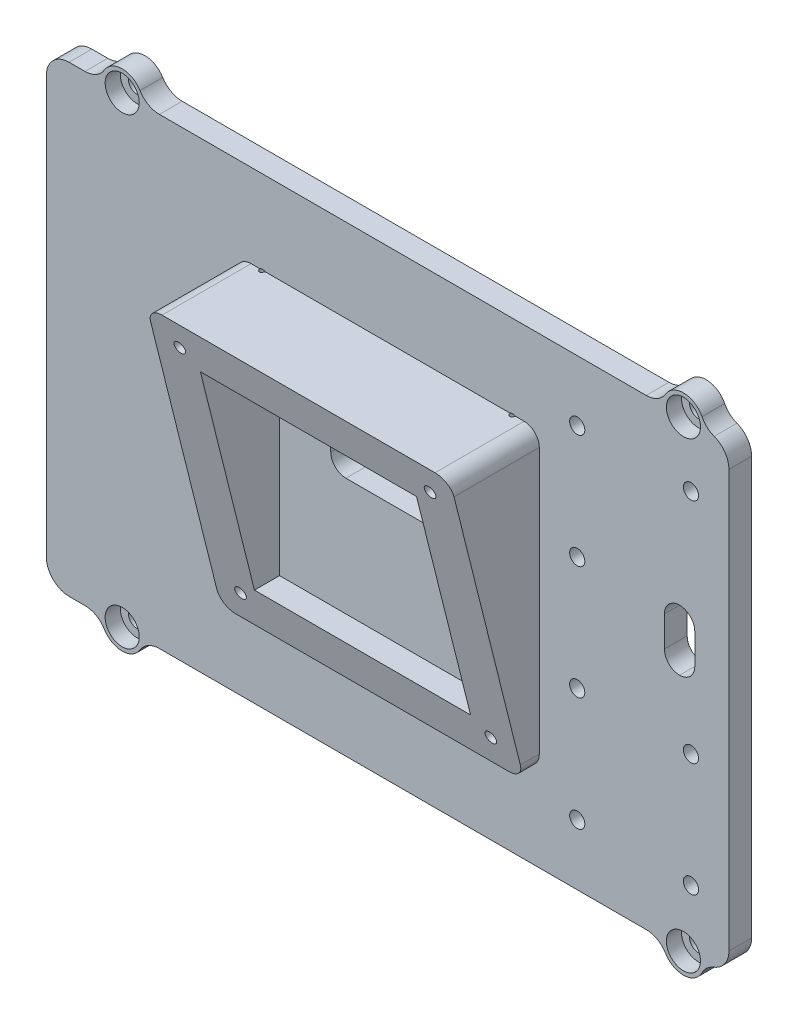
SolidWorks part; units mm, degrees
ref_plane "Спереди" through (0, 0, 0) normal (0, 0, 1) x (1, 0, 0)
ref_plane "Сверху" through (0, 0, 0) normal (0, 1, 0) x (1, 0, 0)
ref_plane "Справа" through (0, 0, 0) normal (1, 0, 0) x (0, 0, -1)
sketch "Эскиз1" plane through (0, 0, 0) normal (0, 1, 0) x (1, 0, 0)
  line L0 (0, 45) -> (0, -45) construction
  line L1 (-30.5, 45) -> (30.5, 45)
  line L2 (-30.5, 45) -> (-30.5, -45)
  line L3 (-30.5, -45) -> (30.5, -45)
  line L4 (30.5, 45) -> (30.5, -45)
  line L6 (-30.5, 0) -> (30.5, 0) construction
  point P8 (0, 0)
  dimension "D1" = 90
  dimension "D2" = 61
extrude "боковые стенки" [suppressed] add sketch "Эскиз1" along normal blind 18
sketch "Эскиз7" plane through (0, 0, 0) normal (0, 1, 0) x (1, 0, 0)
  line L1 (-30.5, 45) -> (30.5, 45)
  line L2 (-30.5, 45) -> (-30.5, -45)
  line L3 (-30.5, -45) -> (30.5, -45)
  line L4 (30.5, 45) -> (30.5, -45)
extrude "крышка" [suppressed] add sketch "Эскиз7" along normal blind 12
dome "Купол6" [suppressed] faces to dome 1 distance 10 parameters "D1"=10
shell "Оболочка1" [suppressed] thickness 2
sketch "Эскиз11" [suppressed] plane through (-30.5, 0, 0) normal (-1, 0, 0) x (0, 0, 1)
  line L1 (-45, 30) -> (45, 30) construction
  line L2 (0, 30) -> (45, 30)
  line L4 (45, 30) -> (45, 18)
  ellipse E0 centre (0, 18) end of major axis (-45, 18) minor radius 12 (45, 18) -> (0, 30) ccw
  dimension "D1" = 12
extrude "скругление вдоль" [suppressed] cut sketch "Эскиз11" against normal through all
sketch "Эскиз12" [suppressed] plane through (0, 0, -45) normal (0, 0, -1) x (-1, 0, 0)
  line L0 (-30.5, 30) -> (-30.5, 0) construction
  line L1 (-30.5, 18) -> (-30.5, 30)
  line L2 (-30.5, 30) -> (30.5, 30) construction
  line L3 (-30.5, 30) -> (0, 30)
  ellipse E0 centre (0, 18) end of major axis (-30.5, 18) minor radius 12 (0, 30) -> (-30.5, 18) ccw
  dimension "D1" = 12
extrude "скругление поперек" [suppressed] cut sketch "Эскиз12" against normal through all
mirror "Зеркальное отражение3" [suppressed] about plane through (0, 0, 0) normal (0, 0, 1)
mirror "Зеркальное отражение4" [suppressed] about plane through (0, 0, 0) normal (1, 0, 0)
shell "Оболочка5" [suppressed] thickness 2.1
sketch "Эскиз13" [suppressed] plane through (30.5, 0, 0) normal (1, 0, 0) x (0, 0, -1)
  line L0 (-45, 30) -> (-45, 0) construction
  line L1 (-36.15, 1) -> (-27.65, 1)
  line L2 (-36.15, 1) -> (-36.15, 0)
  line L3 (-36.15, 0) -> (-27.65, 0)
  line L4 (-27.65, 1) -> (-27.65, 0)
  line L5 (-45, 0) -> (45, 0) construction
  dimension "D1" = 8.5
  dimension "D3" = 8.85
  dimension "D4" = 1
extrude "отверстие для microusb" [suppressed] cut sketch "Эскиз13" against normal up to surface (2.1 mm away)
sketch "Эскиз14" [suppressed] plane through (30.5, 0, 0) normal (1, 0, 0) x (0, 0, -1)
  line L0 (-45, 30) -> (-45, 0) construction
  line L1 (-18.5, 4.5) -> (-2.5, 4.5)
  line L2 (-18.5, 4.5) -> (-18.5, 0)
  line L3 (-18.5, 0) -> (-2.5, 0)
  line L4 (-2.5, 4.5) -> (-2.5, 0)
  line L5 (-45, 0) -> (-36.15, 0) construction
  line L6 (-27.65, 0) -> (45, 0) construction
  dimension "D1" = 16
  dimension "D3" = 26.5
  dimension "D4" = 4.5
extrude "отверстие для hdmi" [suppressed] cut sketch "Эскиз14" against normal up to surface (2.1 mm away)
sketch "Эскиз15" [suppressed] plane through (30.5, 0, 0) normal (1, 0, 0) x (0, 0, -1)
  line L0 (-45, 30) -> (-45, 0) construction
  line L1 (-2.5, 0) -> (45, 0) construction
  circle A0 centre (11, 0.1) radius 3.5
  dimension "D1" = 7
  dimension "D2" = 56
  dimension "D3" = 0.1
extrude "отверстие для audio" [suppressed] cut sketch "Эскиз15" against normal up to surface (2.1 mm away)
sketch "Эскиз16" [suppressed] plane through (0, 0, -45) normal (0, 0, -1) x (-1, 0, 0)
  line L0 (-30.5, 0) -> (30.5, 0) construction
  line L1 (-26.5, 0) -> (-9, 0)
  line L2 (-26.5, 0) -> (-26.5, 11.5)
  line L3 (-26.5, 11.5) -> (-9, 11.5)
  line L4 (-9, 0) -> (-9, 11.5)
  line L5 (-30.5, 30) -> (-30.5, 0) construction
  dimension "D1" = 4
  dimension "D2" = 11.5
  dimension "D3" = 17.5
extrude "отверстие для ethernet" [suppressed] cut sketch "Эскиз16" against normal up to surface (2.1 mm away)
sketch "Эскиз17" [suppressed] plane through (0, 0, -45) normal (0, 0, -1) x (-1, 0, 0)
  line L0 (-9, 0) -> (30.5, 0) construction
  line L1 (-9, 14) -> (26.75, 14)
  line L2 (-9, 14) -> (-9, 0)
  line L3 (-9, 0) -> (26.75, 0)
  line L4 (26.75, 14) -> (26.75, 0)
  dimension "D2" = 35.75
  dimension "D3" = 14
extrude "отверстие для usb" [suppressed] cut sketch "Эскиз17" against normal up to surface (2.1 mm away)
sketch "Эскиз21" [suppressed] plane through (0, 0, 0) normal (0, 1, 0) x (1, 0, 0)
  line L0 (6.5, 0.5) -> (25.5, 0.5)
  line L1 (6.5, 3.5) -> (25.5, 3.5)
  line L3 (-30.5, -45) -> (30.5, -45) construction
  arc A0 (6.5, 3.5) -> (6.5, 0.5) centre (6.5, 2) ccw
  arc A1 (25.5, 0.5) -> (25.5, 3.5) centre (25.5, 2) ccw
  point P1 (5, 2)
  point P3 (27, 2)
  dimension "D1" = 3
  dimension "D2" = 22
  dimension "D3" = 5
  dimension "D4" = 47
extrude "отверстие для шлейфа камеры" [suppressed] cut sketch "Эскиз21" along normal through all
fillet "Скругление2" [suppressed] radius 1.5
sketch "Эскиз23" [suppressed] plane through (0, 0, 0) normal (0, -1, 0) x (1, 0, 0)
  line L0 (-33, 27) -> (-30.5, 27)
  line L1 (-33, 23) -> (0, 23) construction
  line L2 (-33, 23) -> (-33, 0) construction
  line L3 (-33, 0) -> (0, 0) construction
  line L4 (0, 23) -> (0, 0) construction
  line L5 (-30.5, -43.5) -> (-30.5, 43.5) construction
  line L6 (-30.5, 27) -> (-30.5, 19)
  line L7 (-30.5, 19) -> (-33, 19)
  line L8 (-30.5, -19) -> (-33, -19)
  line L9 (-30.5, -27) -> (-30.5, -19)
  line L10 (-33, -27) -> (-30.5, -27)
  line L11 (33, -27) -> (30.5, -27)
  line L12 (30.5, -27) -> (30.5, -19)
  line L13 (30.5, -19) -> (33, -19)
  line L14 (30.5, 36.15) -> (33, 36.15)
  line L15 (30.5, 43.5) -> (30.5, 36.15)
  line L16 (33, 43.5) -> (30.5, 43.5)
  line L17 (28.4, 36.15) -> (30.5, 36.15) construction
  line L18 (30.5, 45) -> (30.5, 36.15) construction
  circle A0 centre (-33, 23) radius 1.65
  arc A1 (-33, 27) -> (-33, 19) centre (-33, 23) ccw
  arc A2 (-33, -27) -> (-33, -19) centre (-33, -23) cw
  circle A3 centre (-33, -23) radius 1.65
  circle A4 centre (33, -23) radius 1.65
  arc A5 (33, -27) -> (33, -19) centre (33, -23) ccw
  arc A6 (33, 43.5) -> (33, 36.15) centre (33, 39.825) cw
  circle A7 centre (33, 39.825) radius 1.65
  dimension "D3" = 3.3
  dimension "D4" = 8
  dimension "D1" = 33
  dimension "D2" = 23
extrude "крепление к корпусу" [suppressed] add sketch "Эскиз23" against normal blind 5
sketch "Эскиз25" [suppressed] plane through (30.5, 0, 0) normal (1, 0, 0) x (0, 0, -1)
  line L0 (-43.5, 18) -> (43.5, 18) construction
  line L1 (-34.5, 18) -> (15.5, 18)
  line L2 (-34.5, 18) -> (-34.5, 0)
  line L3 (-34.5, 0) -> (15.5, 0)
  line L4 (15.5, 18) -> (15.5, 0)
  line L5 (-43.5, 18) -> (-43.5, 5) construction
  line L6 (42.9, 0) -> (-42.9, 0) construction
  dimension "D1" = 9
  dimension "D2" = 50
extrude "Вырез под Г-образные выводы" [suppressed] cut sketch "Эскиз25" against normal up to next
ref_plane "Плоскость1" [suppressed] through (0, 30, 0) normal (0, 1, 0) x (1, 0, 0)
sketch "Эскиз27" [suppressed] plane through (0, 30, 0) normal (0, 1, 0) x (1, 0, 0)
  line L1 (-2.77, -37) -> (19.73, -37)
  line L2 (-2.77, -37) -> (-2.77, -45)
  line L3 (-2.77, -45) -> (19.73, -45)
  line L4 (19.73, -37) -> (19.73, -45)
  line L6 (30.5, -43.5) -> (30.5, -36.15) construction
  line L7 (29, -45) -> (-29, -45) construction
  dimension "D1" = 8
  dimension "D2" = 22.5
  dimension "D3" = 10.77
extrude "Вырез под клемники (подвод питания для серв и шилда)" [suppressed] cut sketch "Эскиз27" against normal up to next
sketch "Эскиз29" plane through (0, 0, 0) normal (0, 0, 1) x (1, 0, 0)
  line L1 (-45, 30.5) -> (45, 30.5)
  line L2 (-45, 30.5) -> (-45, -30.5)
  line L3 (-45, -30.5) -> (45, -30.5)
  line L4 (45, 30.5) -> (45, -30.5)
  point P5 (0, -30.5)
  point P7 (45, 0)
  dimension "D1" = 90
  dimension "D2" = 61
extrude "Основа крышки" add sketch "Эскиз29" along normal mid plane 3
sketch "Эскиз30" plane through (0, 0, 1.5) normal (0, 0, 1) x (1, 0, 0)
  line L0 (45, 30.5) -> (-45, 30.5) construction
  line L5 (45, -30.5) -> (45, 30.5) construction
  line L6 (36.5, 8.75) -> (40.5, 8.75)
  line L7 (36.5, 8.75) -> (36.5, 0.75)
  line L8 (36.5, 0.75) -> (40.5, 0.75)
  line L9 (40.5, 8.75) -> (40.5, 0.75)
  point P6 (36.5, 4.75)
  dimension "D1" = 8
  dimension "D2" = 4
  dimension "D3" = 4.5
  dimension "D4" = 25.75
extrude "Под винты клеммника" cut sketch "Эскиз30" against normal up to next
sketch "Эскиз31" plane through (0, 0, 1.5) normal (0, 0, 1) x (1, 0, 0)
  line L1 (-12.75, 25.5) -> (8.75, 25.5)
  line L2 (-12.75, 25.5) -> (-12.75, 21.5)
  line L3 (-12.75, 21.5) -> (8.75, 21.5)
  line L4 (8.75, 25.5) -> (8.75, 21.5)
  line L5 (45, 30.5) -> (-45, 30.5) construction
  line L6 (-45, 30.5) -> (-45, -30.5) construction
  point P4 (-2, 25.5)
  dimension "D1" = 21.5
  dimension "D2" = 43
  dimension "D3" = 4
  dimension "D4" = 5
extrude "Под шлейф камеры" [suppressed] cut sketch "Эскиз31" against normal through all
sketch "Эскиз32" plane through (0, 0, 1.5) normal (0, 0, 1) x (1, 0, 0)
  line L1 (45, 30.5) -> (-45, 30.5) construction
  line L2 (45, -30.5) -> (45, 30.5) construction
  circle A0 centre (2, 0.5) radius 3
  dimension "D1" = 6
  dimension "D2" = 30
  dimension "D3" = 43
extrude "Под кнопку RESET" [suppressed] cut sketch "Эскиз32" against normal through all
fillet "Скругление3" radius 3 4 edges at (-45, -30.5, 0) (-45, 30.5, 0) (45, 30.5, 0) (45, -30.5, 0)
sketch "Эскиз33" plane through (0, 0, 1.5) normal (0, 0, 1) x (1, 0, 0)
  line L0 (-45, 0) -> (0, 0) construction
  line L1 (-45, 27.5) -> (-45, -27.5) construction
  line L2 (0, 0) -> (0, -30.5) construction
  line L3 (-42, -30.5) -> (42, -30.5) construction
  line L4 (-37.75, -30.5) -> (-32.25, -30.5)
  line L5 (-37.75, 30.5) -> (-32.25, 30.5)
  line L6 (41.75, -30.5) -> (36.25, -30.5)
  line L7 (45, -27.5) -> (45, 27.5) construction
  line L11 (36.25, 30.5) -> (41.75, 30.5)
  line L13 (42, 30.5) -> (-42, 30.5) construction
  arc A0 (-37.75, -30.5) -> (-32.25, -30.5) centre (-35, -30.5) ccw
  arc A1 (-37.75, 30.5) -> (-32.25, 30.5) centre (-35, 30.5) cw
  arc A2 (41.75, -30.5) -> (36.25, -30.5) centre (39, -30.5) cw
  arc A4 (36.25, 30.5) -> (41.75, 30.5) centre (39, 30.5) cw
  point P33 (39, 30.5)
  point P35 (39, -30.5)
  dimension "D1" = 2.75
  dimension "D3" = 6
  dimension "D2" = 10
extrude "Наплывы под шурупы для крепления с корпусом" add sketch "Эскиз33" against normal up to surface (3 mm away) up to face at (38.5, 4.75, -1.5)
sketch "Эскиз34" plane through (0, 0, 1.5) normal (0, 0, 1) x (1, 0, 0)
  circle A0 centre (-35, -30.5) radius 1.2
  circle A1 centre (39, -30.5) radius 1.2
  circle A3 centre (-35, 30.5) radius 1.2
  circle A4 centre (39, 30.5) radius 1.2
  arc A7 (41.75, 30.5) -> (36.25, 30.5) centre (39, 30.5) ccw construction
  dimension "D1" = 2.4
extrude "Отверстия под шурупы для крепления с корпусом" cut sketch "Эскиз34" against normal up to next
sketch "Эскиз35" plane through (0, 0, 1.5) normal (0, 0, 1) x (1, 0, 0)
  circle A0 centre (-35, -30.5) radius 2.25
  circle A1 centre (-35, 30.5) radius 2.25
  circle A3 centre (39, -30.5) radius 2.25
  circle A5 centre (39, 30.5) radius 2.25
  dimension "D1" = 4.5
extrude "Углубления под шляпки" cut sketch "Эскиз35" against normal blind 2
fillet "Скругление под шлейф" [suppressed] radius 2
fillet "Скругление5" radius 2 4 edges at (36.5, 0.75, 0) (40.5, 0.75, 0) (40.5, 8.75, 0) (36.5, 8.75, 0)
sketch "Эскиз39" plane through (0, 0, 1.5) normal (0, 0, 1) x (1, 0, 0)
  line L2 (45, -27.5) -> (45, 27.5) construction
  line L3 (-32.25, -30.5) -> (36.25, -30.5) construction
  circle A0 centre (16.5, -4) radius 12.5
  dimension "D1" = 25
  dimension "D2" = 28.5
  dimension "D3" = 26.5
extrude "Под вентилятор" [suppressed] cut sketch "Эскиз39" against normal up to next
sketch "Эскиз36" plane through (0, 0, 1.5) normal (0, 0, 1) x (1, 0, 0)
  line L1 (-20, 19.5) -> (20, 19.5)
  line L2 (-20, 19.5) -> (-20, -19.5)
  line L3 (-20, -19.5) -> (20, -19.5)
  line L4 (20, 19.5) -> (20, -19.5)
  line L5 (-14.25, 14.25) -> (14.25, 14.25)
  line L6 (-14.25, 14.25) -> (-14.25, -14.25)
  line L7 (-14.25, -14.25) -> (14.25, -14.25)
  line L8 (14.25, 14.25) -> (14.25, -14.25)
  line L11 (-45, 27.5) -> (-45, -27.5) construction
  point P12 (-14.25, 0)
  point P13 (-20, 0)
  point P18 (0, 14.25)
  point P20 (0, 19.5)
  point P21 (14.25, 0)
  point P22 (20, 0)
  dimension "D1" = 39
  dimension "D2" = 40
  dimension "D3" = 28.5
  dimension "D4" = 45
extrude "Выступ для крепления дисплея" add sketch "Эскиз36" along normal blind 12
chamfer "Фаска2" distance 10 distance2 40 1 edges at (0, -19.5, 13.5) first distance on face at (0, -19.5, 7.5)
sketch "Эскиз37" plane through (0, -1.9706, 7.8824) normal (0, -0.2425, 0.9701) x (1, 0, 0)
  line L0 (-16.5, 18.6314) -> (16.5, -14.3686) construction
  line L1 (-16.5, 18.6314) -> (16.5, 18.6314) construction
  line L2 (-16.5, 18.6314) -> (-16.5, -14.3686) construction
  line L3 (-16.5, -14.3686) -> (16.5, -14.3686) construction
  line L4 (16.5, 18.6314) -> (16.5, -14.3686) construction
  line L5 (-16.5, -14.3686) -> (16.5, 18.6314) construction
  line L10 (20, -18.0689) -> (-20, -18.0689) construction
  line L12 (20, 22.1314) -> (-20, 22.1314) construction
  circle A0 centre (-16.5, 18.6314) radius 0.75
  circle A1 centre (16.5, 18.6314) radius 0.75
  circle A2 centre (16.5, -14.3686) radius 0.75
  circle A3 centre (-16.5, -14.3686) radius 0.75
  point P12 (0, -14.3686)
  point P13 (0, 2.1314)
  point P23 (0, 2.1314)
  point P25 (0, -18.0689)
  dimension "D1" = 1.5
  dimension "D2" = 33
  dimension "D4" = 3.5
  dimension "D3" = 4
extrude "Отверстия для креплени дисплея в корпусе" cut sketch "Эскиз37" against normal offset from surface (13.1107 mm away) 1 up to face at (40.2, -30.5, -1.5)
sketch "Эскиз38" plane through (0, 0, 1.5) normal (0, 0, 1) x (1, 0, 0)
  line L1 (-7.5, 9.25) -> (7.5, 9.25)
  line L2 (-7.5, 9.25) -> (-7.5, 1.25)
  line L3 (-7.5, 1.25) -> (7.5, 1.25)
  line L4 (7.5, 9.25) -> (7.5, 1.25)
  line L5 (14.25, 14.25) -> (-14.25, 14.25) construction
  point P4 (0, 9.25)
  point P9 (0, 14.25)
  dimension "D1" = 8
  dimension "D2" = 15
  dimension "D3" = 5
extrude "Под провод дисплея" cut sketch "Эскиз38" against normal up to next
fillet "Скругление6" radius 2 4 edges at (7.5, 1.25, 0) (7.5, 9.25, 0) (-7.5, 9.25, 0) (-7.5, 1.25, 0)
fillet "Скругление7" radius 2 4 edges at (-20, -19.5, 2.5) (20, -19.5, 2.5) (20, 19.5, 7.375) (-20, 19.5, 7.375)
fillet "Скругление8" radius 3 8 edges at (-37.75, 30.5, 0) (-32.25, 30.5, 0) (36.25, -30.5, 0) (41.75, -30.5, 0) (-32.25, -30.5, 0) (-37.75, -30.5, 0) (36.25, 30.5, 0) (41.75, 30.5, 0)
sketch "Эскиз40" plane through (0, 0, 1.5) normal (0, 0, 1) x (1, 0, 0)
  line L0 (-45, 27.5) -> (-45, -27.5) construction
  line L1 (34.0946, 30.5) -> (-30.0946, 30.5) construction
  line L3 (0, 30.5) -> (0, -30.5) construction
  line L4 (-30.0946, -30.5) -> (34.0946, -30.5) construction
  circle A0 centre (-40, 22.5) radius 1 construction
  circle A1 centre (-40, 7.5) radius 1 construction
  circle A2 centre (-40, -7.5) radius 1 construction
  circle A3 centre (-40, -22.5) radius 1 construction
  circle A4 centre (-25, 22.5) radius 1 construction
  circle A5 centre (-25, 7.5) radius 1 construction
  circle A6 centre (-25, -7.5) radius 1 construction
  circle A7 centre (-25, -22.5) radius 1 construction
  circle A8 centre (25, -22.5) radius 1
  circle A9 centre (25, -7.5) radius 1
  circle A10 centre (25, 7.5) radius 1
  circle A11 centre (25, 22.5) radius 1
  circle A12 centre (40, -22.5) radius 1
  circle A13 centre (40, -7.5) radius 1
  circle A15 centre (40, 22.5) radius 1
  dimension "D1" = 2
  dimension "D5" = 15
  dimension "D2" = 5
  dimension "D3" = 8
  dimension "D6" = 2
  dimension "D7" = 15
  dimension "D4" = 4
extrude "Вентиляционные отверстия" cut sketch "Эскиз40" against normal through all
